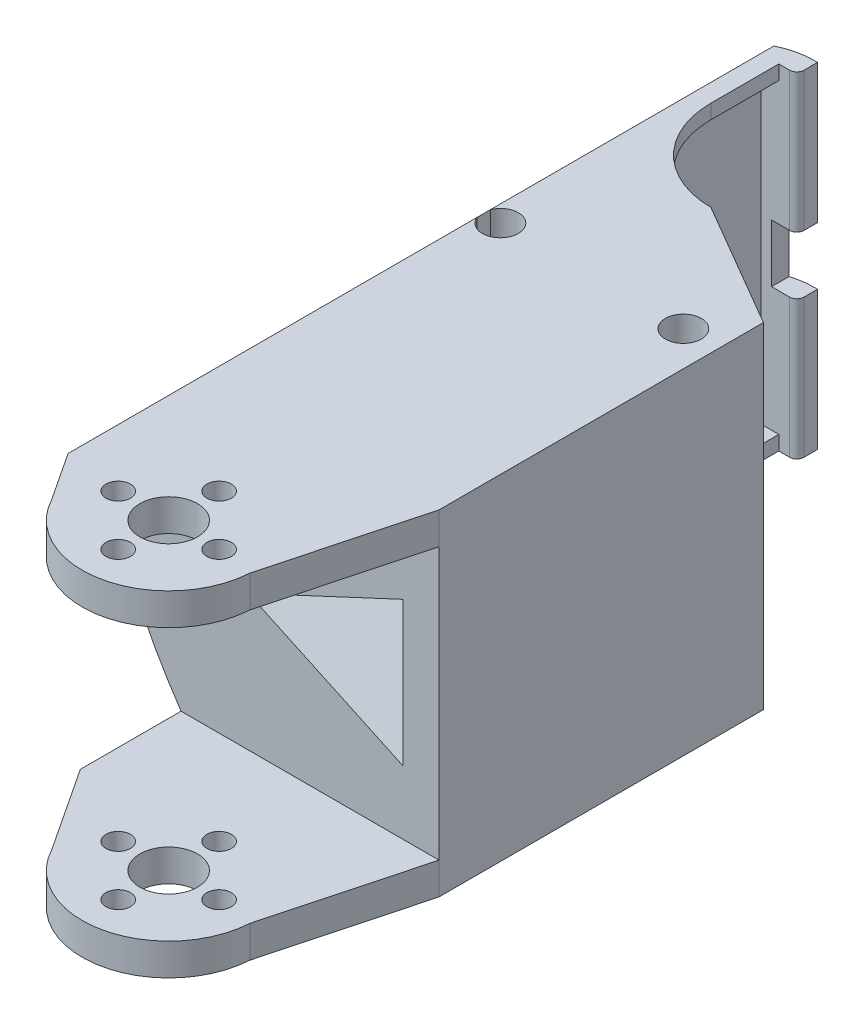
SolidWorks part; units mm, degrees
ref_plane "Front Plane" through (0, 0, 0) normal (0, 0, 1) x (1, 0, 0)
ref_plane "Top Plane" through (0, 0, 0) normal (0, 1, 0) x (1, 0, 0)
ref_plane "Right Plane" through (0, 0, 0) normal (1, 0, 0) x (0, 0, -1)
sketch "Sketch2" plane through (0, 0, 0) normal (0, 1, 0) x (1, 0, 0)
  line L0 (17.5, 0) -> (17.5, 37.7)
  line L1 (-15, 2.5) -> (15, 2.5)
  line L2 (-15, 2.5) -> (-15, 37.7)
  line L4 (15, 2.5) -> (15, 37.7)
  line L5 (17.5, 37.7) -> (15, 37.7)
  line L7 (-17.5, 37.7) -> (-17.5, 0)
  line L8 (-17.5, 0) -> (17.5, 0)
  line L10 (-17.5, 37.7) -> (-15, 37.7)
  point P4 (0, 2.5)
  point P12 (0, 0)
  dimension "D1" = 2.5
  dimension "D2" = 2.5
  dimension "D3" = 37.7
  dimension "D4" = 30
  dimension "D5" = 15
extrude "Boss-Extrude1" add sketch "Sketch2" along normal blind 32.5
sketch "Sketch4" plane through (0, 0, 0) normal (0, -1, 0) x (1, 0, 0)
  line L0 (-17.5, 0) -> (-17.5, -7.4438)
  line L8 (17.5, -7.4438) -> (17.5, 0)
  line L9 (17.5, 0) -> (-17.5, 0)
  line L10 (17.5, 0) -> (17.5, -37.7) construction
  line L13 (-17.5, -7.4438) -> (-17.5, -37.7)
  line L23 (-17.5, -37.7) -> (-15, -37.7)
  line L34 (-15, -37.7) -> (-15, -7.5)
  line L35 (-15, -2.5) -> (-15, -37.7) construction
  line L36 (-15, -7.5) -> (15, -7.5)
  line L37 (15, -37.7) -> (15, -2.5) construction
  line L38 (15, -7.5) -> (15, -37.7)
  line L39 (15, -37.7) -> (17.5, -37.7)
  line L40 (17.5, -37.7) -> (17.5, -7.4438)
  circle A2 centre (-12.6889, -4.95) radius 1.05
  circle A5 centre (12.6889, -4.95) radius 1.05
  dimension "D5" = 2.1
  dimension "D1" = 7.5
  dimension "D6" = 4.8111
  dimension "D7" = 4.95
  dimension "D8" = 4.8111
extrude "Boss-Extrude2" add sketch "Sketch4" along normal blind 2
sketch "Sketch7" plane through (0, -2, 0) normal (0, -1, 0) x (1, 0, 0)
  line L0 (-17.5, 0) -> (-17.5, -37.7)
  line L1 (-17.5, -37.7) -> (-15, -37.7)
  line L2 (-17.5, 0) -> (17.5, 0)
  line L4 (17.5, 0) -> (17.5, -37.7)
  line L5 (17.5, -37.7) -> (15, -37.7)
  line L6 (15, -37.7) -> (15, -7.5)
  line L7 (15, -7.5) -> (-15, -7.5)
  line L8 (-15, -7.5) -> (-15, -37.7)
  circle A2 centre (-12.6889, -4.95) radius 2.495
  circle A3 centre (12.6889, -4.95) radius 2.495
  dimension "D1" = 4.99
extrude "Wire spacing2" add sketch "Sketch7" along normal blind 3
sketch "Sketch8" plane through (0, -5, 0) normal (0, -1, 0) x (1, 0, 0)
  line L0 (-17.5, 0) -> (-17.5, -37.7)
  line L1 (-17.5, -37.7) -> (17.5, -37.7)
  line L2 (17.5, -37.7) -> (17.5, 0) construction
  line L3 (15, -37.7) -> (17.5, -37.7) construction
  line L4 (-17.5, 0) -> (17.5, 0)
  line L6 (17.5, 0) -> (17.5, -37.7)
  circle A0 centre (-12.6889, -4.95) radius 2.495
  circle A1 centre (12.6889, -4.95) radius 2.495
  circle A2 centre (12.6889, -4.95) radius 2.495 construction
  circle A3 centre (-12.6889, -4.95) radius 2.495 construction
extrude "Boss-Extrude6" add sketch "Sketch8" along normal blind 2
sketch "Sketch5" plane through (0, 32.5, 0) normal (0, 1, 0) x (1, 0, 0)
  line L0 (-9.939, 10) -> (-9.939, 2.5)
  line L9 (15, 2.5) -> (-15, 2.5) construction
  line L11 (-12.6889, 12) -> (-9.939, 10)
  line L13 (-17.5, 0) -> (17.5, 0) construction
  line L15 (-17.5, 0) -> (-17.5, 37.7)
  line L17 (12.6889, 12) -> (9.939, 10)
  line L20 (17.5, 0) -> (17.5, 37.7)
  line L21 (-9.939, 2.5) -> (9.939, 2.5)
  line L22 (9.939, 2.5) -> (9.939, 10)
  line L23 (-17.5, 0) -> (17.5, 0)
  line L24 (-12.6889, 12) -> (-15, 12)
  line L25 (-15, 37.7) -> (-15, 7.5) construction
  line L26 (-15, 12) -> (-15, 37.7)
  line L27 (-15, 37.7) -> (-17.5, 37.7)
  line L30 (17.5, 37.7) -> (15, 37.7)
  line L31 (15, 37.7) -> (15, 12)
  line L32 (15, 7.5) -> (15, 37.7) construction
  line L33 (15, 12) -> (12.6889, 12)
  circle A0 centre (-12.6889, 4.95) radius 1.05 construction
  circle A1 centre (-12.6889, 8.7) radius 1.05
  circle A2 centre (12.6889, 8.7) radius 1.05
  circle A3 centre (12.6889, 4.95) radius 1.05 construction
  point P0 (0, 0)
  dimension "D4" = 0
  dimension "D7" = 8.7
  dimension "D3" = 0
  dimension "D1" = 12
  dimension "D2" = 7.561
  dimension "D5" = 10
  dimension "D6" = 7.561
extrude "Boss-Extrude3" add sketch "Sketch5" along normal blind 2
sketch "Sketch9" plane through (0, 34.5, 0) normal (0, 1, 0) x (1, 0, 0)
  line L0 (-17.5, 0) -> (-17.5, 37.7)
  line L1 (-17.5, 37.7) -> (-15, 37.7)
  line L2 (-15, 37.7) -> (-15, 12)
  line L3 (-15, 12) -> (-12.6889, 12)
  line L4 (-12.6889, 12) -> (-9.939, 10)
  line L5 (-9.939, 10) -> (-9.939, 2.5)
  line L6 (-9.939, 2.5) -> (9.939, 2.5)
  line L7 (9.939, 2.5) -> (9.939, 10)
  line L8 (9.939, 10) -> (12.6889, 12)
  line L9 (12.6889, 12) -> (9.939, 10) construction
  line L10 (12.6889, 12) -> (15, 12)
  line L11 (15, 7.5) -> (15, 37.7) construction
  line L12 (15, 12) -> (15, 37.7)
  line L13 (15, 37.7) -> (17.5, 37.7)
  line L14 (17.5, 0) -> (17.5, 37.7) construction
  line L15 (17.5, 37.7) -> (15, 37.7) construction
  line L16 (17.5, 37.7) -> (17.5, 0)
  line L17 (17.5, 0) -> (-17.5, 0)
  line L18 (15, 12) -> (12.6889, 12) construction
  circle A0 centre (-12.6889, 8.7) radius 2.495
  circle A1 centre (12.6889, 8.7) radius 2.495
  point P38 (15, 13.0012)
  dimension "D1" = 4.99
  dimension "D2" = 0
extrude "Wire spacing1" add sketch "Sketch9" along normal blind 3
sketch "Sketch10" plane through (0, 37.5, 0) normal (0, 1, 0) x (1, 0, 0)
  line L1 (-17.5, 37.7) -> (17.5, 37.7)
  line L2 (-17.5, 37.7) -> (-17.5, 0)
  line L3 (-17.5, 0) -> (17.5, 0)
  line L4 (17.5, 37.7) -> (17.5, 0)
  circle A0 centre (-12.6889, 8.7) radius 2.495
  circle A1 centre (12.6889, 8.7) radius 2.495
  circle A2 centre (-12.6889, 8.7) radius 2.495 construction
  circle A3 centre (12.6889, 8.7) radius 2.495 construction
extrude "Boss-Extrude8" add sketch "Sketch10" along normal blind 2
sketch "Sketch11" plane through (0, 39.5, 0) normal (0, 1, 0) x (1, 0, 0)
  line L0 (17.5, 37.7) -> (-17.5, 37.7) construction
  circle A0 centre (0, 37.7) radius 12.5
  dimension "D1" = 25
extrude "Cut-Extrude1" cut sketch "Sketch11" against normal through all
sketch "Sketch12" plane through (0, -7, 0) normal (0, -1, 0) x (1, 0, 0)
  line L4 (0, -25.2) -> (17.5, -15)
  line L5 (17.5, -37.7) -> (17.5, 0) construction
  line L6 (17.5, -15) -> (17.5, -47.4845)
  line L7 (17.5, -47.4845) -> (0, -25.2)
  line L8 (17.5, 0) -> (-17.5, 0) construction
  arc A1 (12.5, -37.7) -> (-12.5, -37.7) centre (0, -37.7) ccw construction
  dimension "D1" = 15
extrude "Cut-Extrude2" cut sketch "Sketch12" against normal through all
sketch "Sketch13" plane through (0, 0, 0) normal (0, 0, 1) x (1, 0, 0)
  line L0 (17.5, -7) -> (-17.5, -7) construction
  line L1 (17.5, 39.5) -> (-27.5, 39.5)
  line L2 (17.5, 39.5) -> (17.5, -7)
  line L3 (17.5, -7) -> (-27.5, -7)
  line L4 (-27.5, 39.5) -> (-27.5, -7)
  line L5 (-17.5, 39.5) -> (-17.5, -7) construction
  dimension "D1" = 10
extrude "Boss-Extrude9" add sketch "Sketch13" along normal blind 30
sketch "Sketch15" plane through (0, 0, 0) normal (0, 0, -1) x (-1, 0, 0)
  line L0 (17.5, -7) -> (12.5, -7) construction
  line L1 (27.5, 39.5) -> (15, 39.5)
  line L2 (27.5, 39.5) -> (27.5, -7)
  line L3 (27.5, -7) -> (15, -7)
  line L4 (15, 39.5) -> (15, -7)
extrude "Boss-Extrude10" add sketch "Sketch15" along normal blind 50
sketch "Sketch18" plane through (0, -7, 0) normal (0, -1, 0) x (1, 0, 0)
  line L0 (12.5, 35) -> (12.5, 30)
  line L1 (12.5, 30) -> (-12.5, 30)
  line L2 (-12.5, 35) -> (-12.5, 30)
  line L3 (12.5, 35) -> (9.3675, 42.5)
  line L4 (-9.3675, 42.5) -> (-12.5, 35)
  line L5 (-27.5, 30) -> (17.5, 30) construction
  circle A0 centre (0, 50) radius 4
  arc A1 (9.3675, 42.5) -> (-9.3675, 42.5) centre (0, 50) ccw
  circle A2 centre (0, 43) radius 1.7
  circle A3 centre (-7, 50) radius 1.7
  circle A4 centre (0, 57) radius 1.7
  circle A5 centre (7, 50) radius 1.7
  point P11 (7.7726, 26.3901)
  point P12 (0, 30)
  dimension "D3" = 8
  dimension "D5" = 12
  dimension "D7" = 3.4
  dimension "D1" = 25
  dimension "D2" = 20
  dimension "D4" = 5
  dimension "D6" = 12.5
  dimension "D8" = 7
  dimension "D9" = 7
  dimension "D10" = 7
  dimension "D11" = 7
  dimension "D12" = 0
  dimension "D13" = 0
extrude "Boss-Extrude11" add sketch "Sketch18" against normal up to surface (46.5 mm away) up to face at (-12.5969, 39.5, -8.7)
sketch "Sketch22" plane through (0, -7, 0) normal (0, -1, 0) x (1, 0, 0)
  line L0 (-27.5, 30) -> (-9.3341, 57.5416)
  line L1 (-9.3341, 57.5416) -> (-9.3341, 30)
  line L2 (-9.3341, 30) -> (-27.5, 30)
  line L4 (17.5, 30) -> (10.749, 55.3347)
  line L5 (10.749, 55.3347) -> (7.9223, 30)
  line L6 (7.9223, 30) -> (17.5, 30)
  arc A0 (9.3675, 42.5) -> (-9.3675, 42.5) centre (0, 50) ccw construction
  point P7 (-9.3341, 30)
  point P12 (-27.3956, 30.1578)
extrude "Boss-Extrude13" add sketch "Sketch22" against normal up to surface (46.5 mm away) up to face at (-12.5969, 39.5, -8.7)
sketch "Sketch21" plane through (-27.5, 0, 0) normal (-1, 0, 0) x (0, 0, 1)
  line L1 (107.4125, 35.075) -> (30, 35.075)
  line L2 (107.4125, 35.075) -> (107.4125, -2.575)
  line L3 (107.4125, -2.575) -> (30, -2.575)
  line L4 (30, 35.075) -> (30, -2.575)
  line L6 (-50, -7) -> (-50, 39.5) construction
  line L7 (30, 39.5) -> (30, -7) construction
  point P6 (-50, 16.25)
  point P7 (30, 16.25)
  dimension "D1" = 37.65
  dimension "D2" = 0
extrude "Cut-Extrude3" cut sketch "Sketch21" against normal through all
sketch "Sketch26" plane through (0, 39.5, 0) normal (0, 1, 0) x (1, 0, 0)
  line L0 (-27.5, -30) -> (-27.5, 50) construction
  line L1 (-27.5, 29.3872) -> (-27.5, 50)
  line L2 (-27.5, 50) -> (-15, 50)
  spline S0 degree 2 poles (-15, 50) (-23.5947, 41.1535) (-27.5, 29.3872) knots 0 0 0 1 1 1
extrude "Cut-Extrude5" cut sketch "Sketch26" against normal through all
sketch "Sketch24" plane through (0, 0, 0) normal (0, 0, -1) x (-1, 0, 0)
  line L4 (15, -7) -> (27.5, -7)
  line L5 (27.5, -7) -> (27.5, 16.25)
  spline S0 degree 2 poles (27.5, 16.25) (23.3985, 3.4824) (15, -7) knots 0 0 0 1 1 1
extrude "Cut-Extrude4" cut sketch "Sketch24" against normal through all both and the other way through all
ref_plane "Plane1" through (0, 16.25, 0) normal (0, -1, 0) x (-1, 0, 0)
mirror "Mirror1" about plane through (0, 16.25, 0) normal (0, -1, 0) of "Cut-Extrude4"
sketch "Sketch27" plane through (0, 0, -2.5) normal (0, 0, -1) x (-1, 0, 0)
  line L0 (-12.5, 26.25) -> (8.9451, 16.25)
  line L1 (-17.875, 16.25) -> (17.875, 16.25) construction
  line L2 (8.9451, 16.25) -> (-12.5, 6.25)
  line L4 (-12.5, 6.25) -> (-12.5, 26.25)
  line L5 (-15, 32.5) -> (-15, 0) construction
  point P7 (-12.5, 16.25)
  point P8 (22.4768, 16.25)
  dimension "D1" = 50
  dimension "D2" = 20
  dimension "D3" = 2.5
extrude "Cut-Extrude6" cut sketch "Sketch27" against normal through all
sketch "Sketch28" plane through (0, 39.5, 0) normal (0, 1, 0) x (1, 0, 0)
  line L0 (-15, 37.7) -> (-15, 50)
  line L1 (-15, 50) -> (-10, 50)
  line L2 (-10, 50) -> (-10, 47.127)
  line L3 (-10, 47.127) -> (-12.5, 47.127)
  line L4 (-12.5, 47.127) -> (-12.5, 37.7)
  line L5 (-15, 37.7) -> (-12.5, 37.7)
  dimension "D1" = 2.5
extrude "Boss-Extrude14" add sketch "Sketch28" against normal up to surface (46.5 mm away) up to face at (-3.2058, -7, 7.0935)
fillet "Fillet2" radius 10 1 edges at (-15, 16.25, -50)
sketch "Sketch29" plane through (0, 0, -37.7) normal (0, 0, 1) x (1, 0, 0)
  line L1 (-15, 37.5) -> (-12.5, 37.5)
  line L2 (-15, 37.5) -> (-15, -5)
  line L3 (-15, -5) -> (-12.5, -5)
  line L4 (-12.5, 37.5) -> (-12.5, -5)
extrude "Cut-Extrude8" cut sketch "Sketch29" against normal up to surface (9.427 mm away) up to face at (-11.25, 16.25, -47.127)
fillet "Fillet3" radius 1 1 edges at (-10, 16.25, -47.127)
sketch "Sketch30" plane through (0, 0, -47.127) normal (0, 0, 1) x (1, 0, 0)
  line L0 (-17.875, 16.25) -> (17.875, 16.25) construction
  line L1 (-6.1884, 20.25) -> (-13.5, 20.25)
  line L2 (-6.1884, 20.25) -> (-6.1884, 12.25)
  line L3 (-6.1884, 12.25) -> (-13.5, 12.25)
  line L4 (-13.5, 20.25) -> (-13.5, 12.25)
  line L5 (-11, -7) -> (-11, 39.5) construction
  point P4 (-13.5, 16.25)
  dimension "D1" = 8
  dimension "D2" = 2.5
extrude "Cut-Extrude9" cut sketch "Sketch30" against normal blind 22.5
